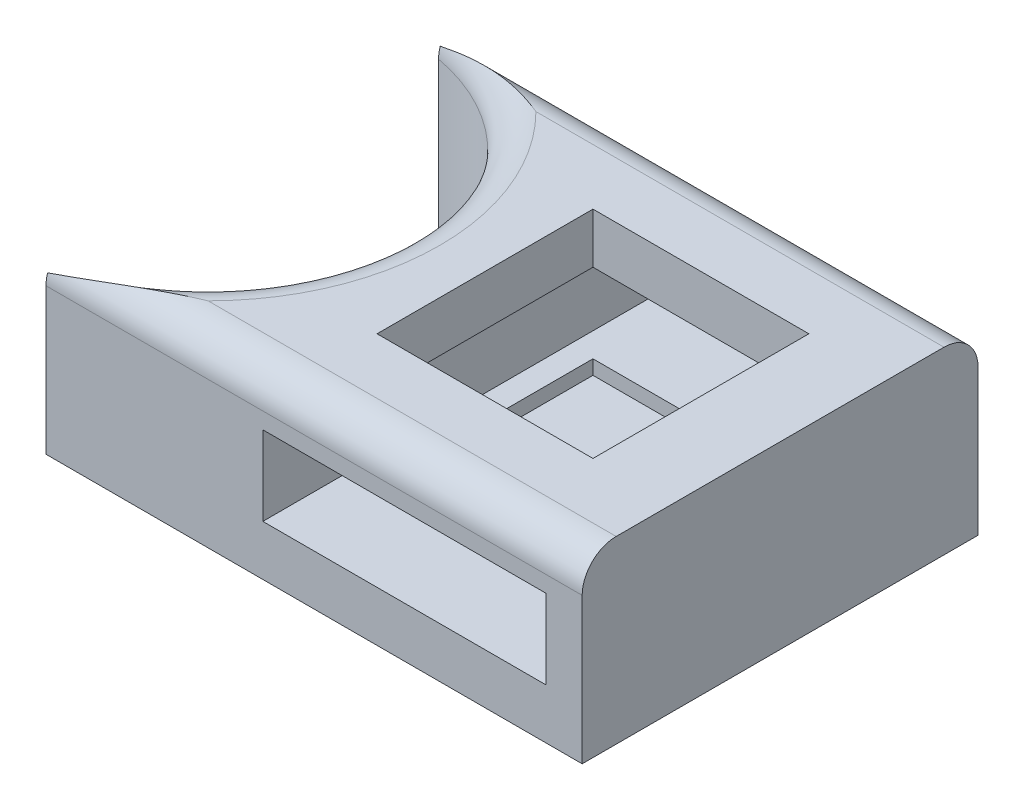
SolidWorks part; units mm, degrees
ref_plane "Front Plane" through (0, 0, 0) normal (0, 0, 1) x (1, 0, 0)
ref_plane "Top Plane" through (0, 0, 0) normal (0, 1, 0) x (1, 0, 0)
ref_plane "Right Plane" through (0, 0, 0) normal (1, 0, 0) x (0, 0, -1)
sketch "Sketch1" plane through (0, 0, 0) normal (0, 1, 0) x (1, 0, 0)
  line L1 (-52.9117, 34.1909) -> (-2.4317, 34.1909)
  line L3 (-52.9117, -0.7341) -> (-2.4317, -0.7341)
  line L4 (-2.4317, 34.1909) -> (-2.4317, -0.7341)
  arc A0 (-52.9117, 34.1909) -> (-52.9117, -0.7341) centre (-52.9117, 16.7284) cw
  dimension "D1" = 50.48
  dimension "D2" = 34.925
extrude "Boss-Extrude1" add sketch "Sketch1" along normal blind 15.875
sketch "Sketch2" plane through (0, 0, 0) normal (0, -1, 0) x (-1, 0, 0)
  line L1 (31.0067, 27.8409) -> (5.6067, 27.8409)
  line L2 (31.0067, 27.8409) -> (31.0067, 24.6659)
  line L3 (31.0067, 24.6659) -> (5.6067, 24.6659)
  line L4 (5.6067, 27.8409) -> (5.6067, 24.6659)
  dimension "D1" = 3.175
  dimension "D2" = 25.4
  dimension "D3" = 3.175
  dimension "D4" = 6.35
extrude "Boss-Extrude2" add sketch "Sketch2" along normal blind 3.175
sketch "Sketch3" plane through (0, 0, 0) normal (0, -1, 0) x (-1, 0, 0)
  line L0 (2.4317, -0.7341) -> (2.4317, 34.1909) construction
  line L1 (31.0067, 8.7909) -> (5.6067, 8.7909)
  line L2 (31.0067, 8.7909) -> (31.0067, 5.6159)
  line L3 (31.0067, 5.6159) -> (5.6067, 5.6159)
  line L4 (5.6067, 8.7909) -> (5.6067, 5.6159)
  dimension "D1" = 3.175
  dimension "D2" = 3.175
  dimension "D3" = 6.35
  dimension "D4" = 25.4
extrude "Boss-Extrude3" add sketch "Sketch3" along normal blind 3.175
sketch "Sketch4" plane through (0, 0, -34.1909) normal (0, 0, -1) x (-1, 0, 0)
  line L0 (49.7367, 15.875) -> (49.7367, 0) construction
  line L1 (2.4317, 15.875) -> (52.9117, 15.875) construction
  line L2 (2.4317, 0) -> (52.9117, 0) construction
  dimension "D1" = 3.175
sketch "Sketch5" plane through (0, 0, -34.1909) normal (0, 0, -1) x (-1, 0, 0)
  line L1 (49.7367, 15.875) -> (52.9117, 15.875)
  line L2 (49.7367, 15.875) -> (49.7367, 0)
  line L3 (49.7367, 0) -> (52.9117, 0)
  line L4 (52.9117, 15.875) -> (52.9117, 0)
extrude "Cut-Extrude1" cut sketch "Sketch5" against normal blind 3.175
sketch "Sketch6" plane through (0, 0, 0.7341) normal (0, 0, 1) x (1, 0, 0)
  line L0 (-49.7367, 15.875) -> (-49.7367, 0) construction
  line L1 (-52.9117, 15.875) -> (-2.4317, 15.875) construction
  line L2 (-52.9117, 0) -> (-2.4317, 0) construction
  line L4 (-52.9117, 15.875) -> (-49.7367, 15.875)
  line L5 (-52.9117, 15.875) -> (-52.9117, 0)
  line L6 (-52.9117, 0) -> (-49.7367, 0)
  line L7 (-49.7367, 15.875) -> (-49.7367, 0)
  dimension "D1" = 3.175
extrude "Cut-Extrude2" cut sketch "Sketch6" against normal blind 3.175
sketch "Sketch7" plane through (0, 15.875, 0) normal (0, 1, 0) x (1, 0, 0)
  line L0 (-35.4492, 16.7284) -> (-2.4317, 16.7284) construction
  line L1 (-2.4317, -0.7341) -> (-2.4317, 34.1909) construction
  line L3 (-28.4654, 7.2034) -> (-9.4154, 7.2034)
  line L4 (-28.4654, 7.2034) -> (-28.4654, 26.2534)
  line L5 (-28.4654, 26.2534) -> (-9.4154, 26.2534)
  line L6 (-9.4154, 7.2034) -> (-9.4154, 26.2534)
  line L7 (-28.4654, 7.2034) -> (-9.4154, 26.2534) construction
  line L8 (-28.4654, 26.2534) -> (-9.4154, 7.2034) construction
  arc A0 (-49.7367, -0.443) -> (-49.7367, 33.8999) centre (-52.9117, 16.7284) ccw construction
  point P7 (-18.9404, 16.7284)
  dimension "D1" = 19.05
  dimension "D2" = 19.05
extrude "Cut-Extrude4" cut sketch "Sketch7" against normal blind 12.7
sketch "Sketch8" plane through (0, 0, -34.1909) normal (0, 0, -1) x (-1, 0, 0)
  line L0 (2.4317, 7.9375) -> (49.6722, 7.9375) construction
  line L1 (2.4317, 15.875) -> (2.4317, 0) construction
  line L3 (30.6067, 4.4375) -> (5.6067, 4.4375)
  line L4 (30.6067, 4.4375) -> (30.6067, 11.4375)
  line L5 (30.6067, 11.4375) -> (5.6067, 11.4375)
  line L6 (5.6067, 4.4375) -> (5.6067, 11.4375)
  line L7 (30.6067, 4.4375) -> (5.6067, 11.4375) construction
  line L8 (30.6067, 11.4375) -> (5.6067, 4.4375) construction
  point P4 (18.1067, 7.9375)
  dimension "D1" = 25
  dimension "D2" = 7
  dimension "D3" = 3.175
extrude "Cut-Extrude5" cut sketch "Sketch8" against normal through all
fillet "Fillet3" radius 3 3 edges at (-26.0842, 15.875, -34.1909) (-26.0842, 15.875, 0.7341) (-35.4492, 15.875, -16.7284)
